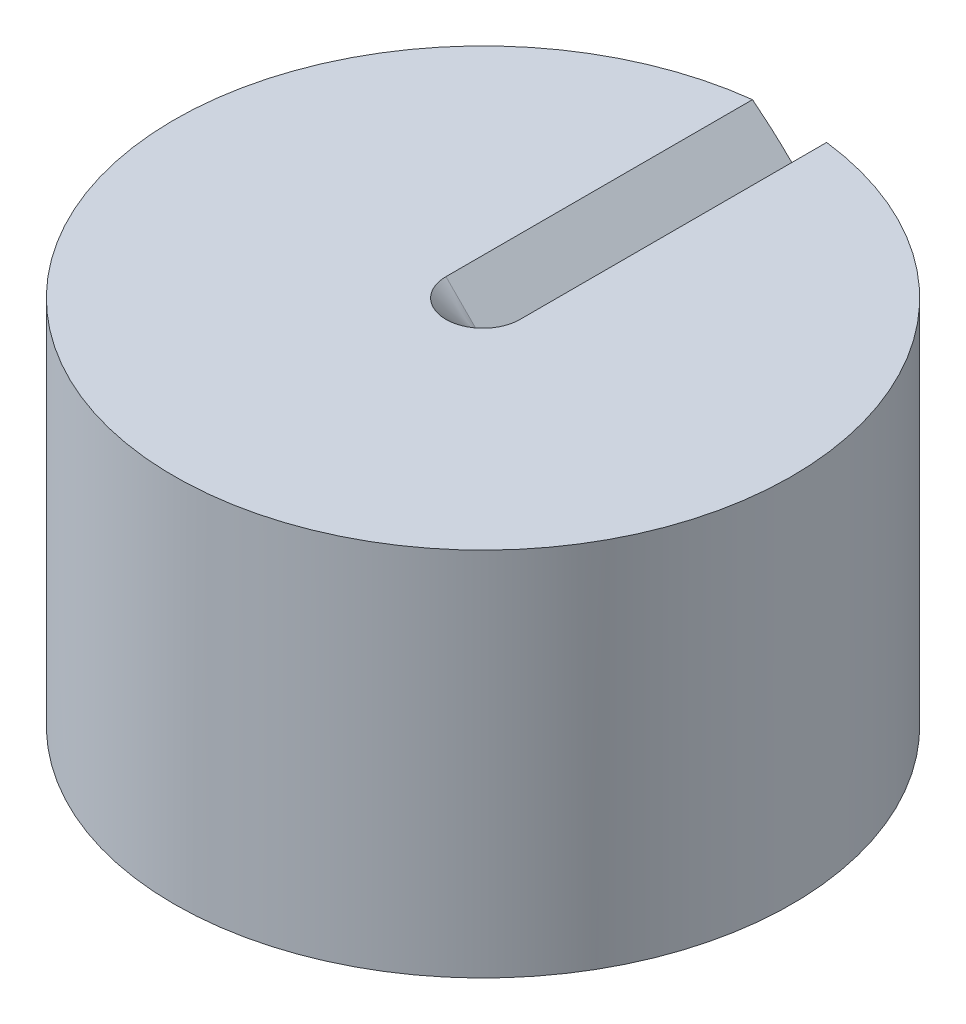
SolidWorks part; units mm, degrees
ref_plane "Front Plane" through (0, 0, 0) normal (0, 0, 1) x (1, 0, 0)
ref_plane "Top Plane" through (0, 0, 0) normal (0, 1, 0) x (1, 0, 0)
ref_plane "Right Plane" through (0, 0, 0) normal (1, 0, 0) x (0, 0, -1)
sketch "Sketch1" plane through (0, 0, 0) normal (0, 1, 0) x (1, 0, 0)
  circle A0 centre (0, 0) radius 19.05
  dimension "D1" = 38.1
extrude "Boss-Extrude1" add sketch "Sketch1" along normal blind 20.32
sketch "Sketch2" plane through (0, 0, 0) normal (0, -1, 0) x (-1, 0, 0)
  circle A0 centre (0, 0) radius 2.9845
  dimension "D1" = 5.969
extrude "Cut-Extrude1" cut sketch "Sketch2" against normal blind 6.858
sketch "Sketch3" plane through (0, 0, 0) normal (0, -1, 0) x (1, 0, 0)
  circle A2 centre (0, 0) radius 5.0165
  circle A3 centre (0, 0) radius 5.0165
  circle A5 centre (0, 0) radius 16.51
  circle A6 centre (0, 0) radius 16.51
  dimension "D1" = 2.032
  dimension "D2" = 2.54
extrude "Cut-Extrude2" cut sketch "Sketch3" against normal offset from surface (15.24 mm away) 5.08 up to face at (0, 20.32, 19.05)
fillet "Fillet1" radius 2.032 1 edges at (0, 15.24, 5.0165)
sketch "Sketch4" plane through (0, 20.32, 0) normal (0, 1, 0) x (1, 0, 0)
  line L0 (-2.54, 0) -> (-2.54, 18.8799)
  line L1 (2.54, 0) -> (2.54, 18.8799)
  arc A0 (-2.54, 0) -> (2.54, 0) centre (0, 0) ccw
  circle A1 centre (0, 0) radius 19.05 construction
  arc A2 (2.54, 18.8799) -> (-2.54, 18.8799) centre (0, 0) ccw
  point P1 (4.4146, 18.5314)
  dimension "D1" = 5.08
extrude "Cut-Extrude3" cut sketch "Sketch4" against normal blind 2.286
chamfer "Chamfer1" distance 2.54 angle 45 3 edges at (2.54, 18.034, -9.44) (0, 18.034, 2.54) (-2.54, 18.034, -9.44)
sketch "Sketch6" plane through (0, 0, 0) normal (0, -1, 0) x (1, 0, 0)
  circle A0 centre (0, 0) radius 16.51
  circle A1 centre (0, 0) radius 19.05
  circle A2 centre (0, 0) radius 19.05 construction
  circle A3 centre (0, 0) radius 16.51 construction
extrude "Boss-Extrude2" add sketch "Sketch6" along normal blind 2.54
